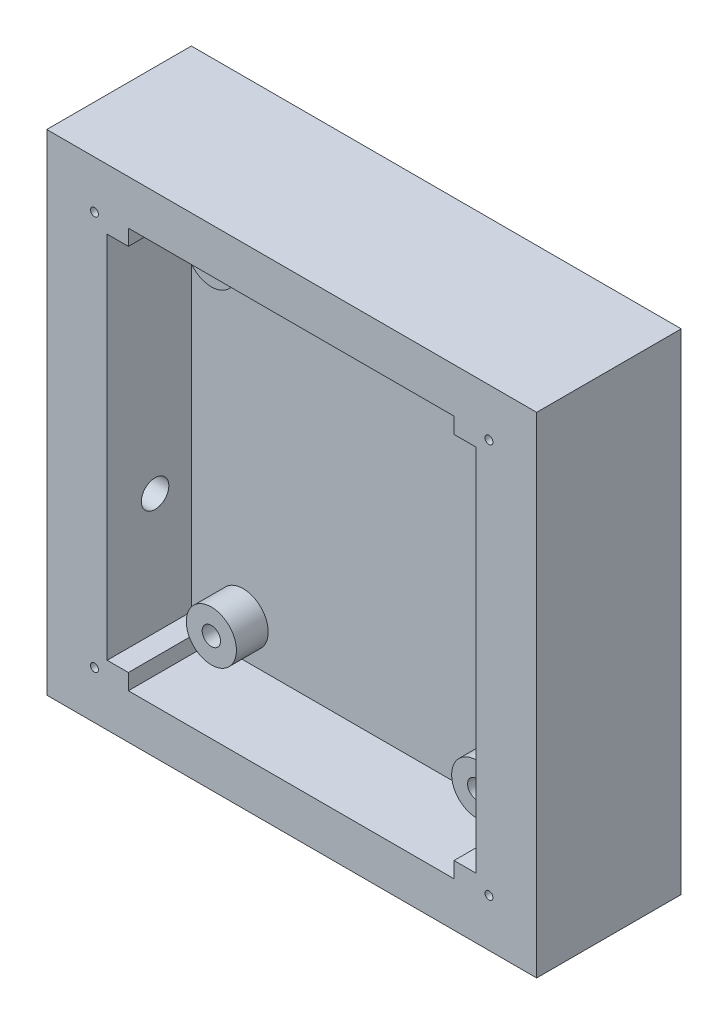
SolidWorks part; units mm, degrees
ref_plane "Plan de face" through (0, 0, 0) normal (0, 0, 1) x (1, 0, 0)
ref_plane "Plan de dessus" through (0, 0, 0) normal (0, 1, 0) x (1, 0, 0)
ref_plane "Plan de droite" through (0, 0, 0) normal (1, 0, 0) x (0, 0, -1)
sketch "Esquisse1" plane through (0, 0, 0) normal (0, 0, 1) x (1, 0, 0)
  line L0 (-0.154, 0) -> (0.154, 0) construction
  line L1 (-0.154, 0.154) -> (0.154, 0.154)
  line L2 (-0.154, 0.154) -> (-0.154, -0.154)
  line L3 (-0.154, -0.154) -> (0.154, -0.154)
  line L4 (0.154, 0.154) -> (0.154, -0.154)
  line L5 (-0.154, 0.154) -> (0.154, -0.154) construction
  line L6 (-0.154, -0.154) -> (0.154, 0.154) construction
  line L7 (0.154, 0) -> (0, 0.154) construction
  line L8 (0, 0.154) -> (0, -0.154) construction
  point P0 (0, 0)
  dimension "D1" = 0.308
  dimension "D2" = 0.308
extrude "Boss.-Extru.1" add sketch "Esquisse1" along normal blind 0.0909
shell "Coque1" thickness 0.038 removed face at (0, 0, 0.0909)
sketch "Esquisse2" plane through (0, 0, 0.0909) normal (0, 0, 1) x (1, 0, 0)
  line L0 (-0.154, 0.154) -> (-0.116, 0.116) construction
  line L1 (-0.154, 0.154) -> (-0.154, -0.154) construction
  line L2 (0.154, 0.154) -> (-0.154, 0.154) construction
  line L3 (-0.154, 0) -> (0.154, 0) construction
  line L4 (0.154, -0.154) -> (0.154, 0.154) construction
  line L5 (0.154, 0.154) -> (-0.154, -0.154) construction
  circle A0 centre (-0.124, 0.124) radius 0.0025
  circle A1 centre (0.124, -0.124) radius 0.0025
  circle A2 centre (0.124, 0.124) radius 0.0025
  circle A3 centre (-0.124, -0.124) radius 0.0025
  dimension "D3" = 0.005
  dimension "D1" = 0.03
  dimension "D2" = 0.03
extrude "Enlèv. mat.-Extru.1" cut sketch "Esquisse2" against normal blind 0.04
sketch "Esquisse3" plane through (0, 0, 0.038) normal (0, 0, 1) x (1, 0, 0)
  line L3 (-0.094, 0) -> (0.094, 0) construction
  line L4 (-0.094, 0.1135) -> (0.094, 0.1135)
  line L5 (-0.094, 0.1135) -> (-0.094, -0.1135)
  line L6 (-0.094, -0.1135) -> (0.094, -0.1135)
  line L7 (0.094, 0.1135) -> (0.094, -0.1135)
  line L8 (-0.094, 0.1135) -> (0.094, -0.1135) construction
  line L9 (-0.094, -0.1135) -> (0.094, 0.1135) construction
  line L10 (0, 0.1135) -> (0, -0.1135) construction
  circle A0 centre (-0.0834, 0.1029) radius 0.0058
  circle A1 centre (-0.0834, -0.1029) radius 0.0058
  circle A2 centre (0.0834, -0.1029) radius 0.0058
  circle A3 centre (0.0834, 0.1029) radius 0.0058
  circle A4 centre (-0.0834, 0.1029) radius 0.0158
  circle A5 centre (-0.0834, -0.1029) radius 0.0158
  circle A6 centre (0.0834, -0.1029) radius 0.0158
  circle A7 centre (0.0834, 0.1029) radius 0.0158
  point P7 (0, 0)
  point P19 (0, 0)
  dimension "D3" = 0.0115
  dimension "D6" = 0.01
  dimension "D1" = 0.188
  dimension "D2" = 0.227
  dimension "D4" = 0.0106
  dimension "D5" = 0.0106
sketch "Esquisse4" plane through (0, 0, 0.0909) normal (0, 0, 1) x (1, 0, 0)
  line L0 (0.116, 0.116) -> (-0.116, 0.116) construction
  line L1 (-0.1027, 0.116) -> (0.1021, 0.116)
  line L2 (-0.1027, 0.116) -> (-0.1027, 0.126)
  line L3 (-0.1027, 0.126) -> (0.1021, 0.126)
  line L4 (0.1021, 0.116) -> (0.1021, 0.126)
  line L5 (-0.154, 0) -> (0.154, 0) construction
  line L6 (-0.154, 0.154) -> (-0.154, -0.154) construction
  line L7 (0.154, -0.154) -> (0.154, 0.154) construction
  line L8 (-0.1027, -0.116) -> (0.1021, -0.116)
  line L9 (0.1021, -0.116) -> (0.1021, -0.126)
  line L10 (-0.1027, -0.116) -> (-0.1027, -0.126)
  line L11 (-0.1027, -0.126) -> (0.1021, -0.126)
extrude "Enlèv. mat.-Extru.2" cut sketch "Esquisse4" against normal blind 0.0529
extrude "Boss.-Extru.2" add sketch "Esquisse3" along normal blind 0.02 contours A7 | A6 | A5 | A4
extrude "Enlèv. mat.-Extru.3" cut sketch "Esquisse3<4>" along normal blind 0.02 contours A1 | A0 | A2 | A3
sketch "Esquisse3<4>" plane through (0, 0, 0.038) normal (0, 0, 1) x (1, 0, 0) same geometry as "Esquisse3"
sketch "Esquisse6" plane through (-0.154, 0, 0) normal (-1, 0, 0) x (0, 0, 1)
  line L0 (0, 0.154) -> (0.0909, -0.154) construction
  line L1 (0.0909, -0.154) -> (0.0909, 0) construction
  line L2 (0.0909, 0.154) -> (0.0909, -0.154) construction
  line L3 (0.0909, 0) -> (0, 0) construction
  line L4 (0, 0) -> (0.0454, -0.154) construction
  line L5 (0.0909, -0.154) -> (0, -0.154) construction
  line L6 (0.0454, -0.154) -> (0.0454, 0.154) construction
  line L7 (0.0909, 0.154) -> (0, 0.154) construction
  circle A0 centre (0.0608, -0.0403) radius 0.0086
extrude "Enlèv. mat.-Extru.4" cut sketch "Esquisse6" against normal blind 0.05
